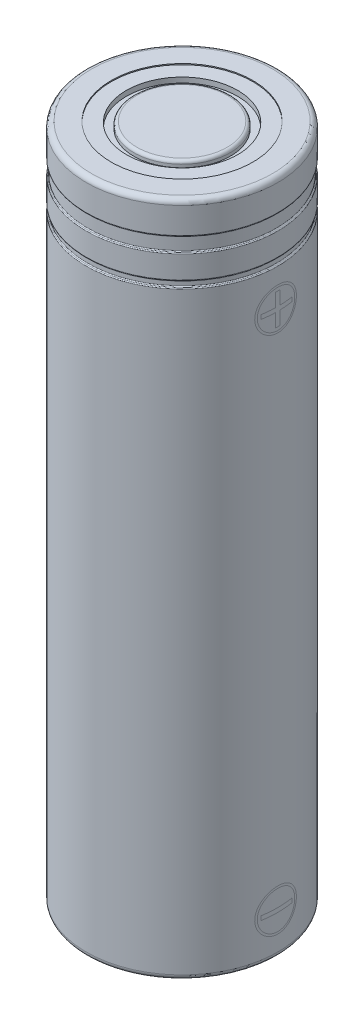
SolidWorks part; units mm, degrees
ref_plane "Front Plane" through (0, 0, 0) normal (0, 0, 1) x (1, 0, 0)
ref_plane "Top Plane" through (0, 0, 0) normal (0, 1, 0) x (1, 0, 0)
ref_plane "Right Plane" through (0, 0, 0) normal (1, 0, 0) x (0, 0, -1)
sketch "Sketch1" plane through (0, 0, 0) normal (0, 0, 1) x (1, 0, 0)
  line L0 (0, 0) -> (0, -7.4) construction
  line L1 (9.2, 57.54) -> (9.2, 0.5)
  line L4 (9.06, 58.1092) -> (9.06, 57.7308)
  line L6 (9.2, 60.46) -> (9.2, 58.3)
  line L8 (9.06, 61.8092) -> (9.06, 60.6508)
  line L9 (9.2, 64.5) -> (9.2, 62)
  line L12 (8.7, 65) -> (6.8, 65)
  line L14 (6.8, 64.9) -> (6.8, 65)
  line L16 (6.8, 64.9) -> (5.35, 64.9)
  line L18 (5.35, 64.4) -> (5.35, 64.9)
  line L20 (5.35, 64.4) -> (4.63, 64.4)
  line L22 (4.63, 64.4) -> (4.63, 64.7)
  line L23 (4.33, 65) -> (0, 65)
  line L25 (8.7, 0) -> (7.9, 0)
  line L27 (7.4, 0) -> (7.4, 0.1)
  line L29 (7.9, 0.1) -> (7.4, 0.1)
  line L32 (0, 0) -> (7.4, 0)
  line L33 (7.9, 0.1) -> (7.9, 0)
  line L34 (0, 65) -> (0, 0)
  line L35 (9.06, 61.8092) -> (9.2, 62) construction
  line L36 (8.7, 64.9) -> (6.8, 64.9)
  line L37 (9.1, 64.5) -> (9.1, 62)
  line L38 (8.96, 61.8092) -> (8.96, 60.6508)
  line L39 (9.1, 60.46) -> (9.1, 58.3)
  line L40 (8.96, 58.1092) -> (8.96, 57.7308)
  line L41 (9.1, 57.54) -> (9.1, 0.5)
  line L42 (8.7, 0.1) -> (7.9, 0.1)
  arc A1 (9.2, 57.54) -> (9.13, 57.6354) centre (9.1, 57.54) ccw
  arc A2 (9.06, 57.7308) -> (9.13, 57.6354) centre (9.16, 57.7308) ccw
  arc A4 (9.13, 58.2046) -> (9.06, 58.1092) centre (9.16, 58.1092) ccw
  arc A6 (9.13, 58.2046) -> (9.2, 58.3) centre (9.1, 58.3) ccw
  arc A9 (9.2, 60.46) -> (9.13, 60.5554) centre (9.1, 60.46) ccw
  arc A10 (9.06, 60.6508) -> (9.13, 60.5554) centre (9.16, 60.6508) ccw
  arc A13 (9.13, 61.9046) -> (9.06, 61.8092) centre (9.16, 61.8092) ccw
  arc A15 (9.13, 61.9046) -> (9.2, 62) centre (9.1, 62) ccw
  arc A17 (9.2, 64.5) -> (8.7, 65) centre (8.7, 64.5) ccw
  arc A19 (4.63, 64.7) -> (4.33, 65) centre (4.33, 64.7) ccw
  arc A21 (8.7, 0) -> (9.2, 0.5) centre (8.7, 0.5) ccw
  arc A22 (9.1, 64.5) -> (8.7, 64.9) centre (8.7, 64.5) ccw
  arc A23 (9.1, 62) -> (8.96, 61.8092) centre (9.16, 61.8092) ccw
  arc A24 (8.96, 60.6508) -> (9.1, 60.46) centre (9.16, 60.6508) ccw
  arc A25 (9.1, 58.3) -> (8.96, 58.1092) centre (9.16, 58.1092) ccw
  arc A26 (8.96, 57.7308) -> (9.1, 57.54) centre (9.16, 57.7308) ccw
  arc A27 (8.7, 0.1) -> (9.1, 0.5) centre (8.7, 0.5) ccw
  point P0 (7.9, 0.05)
  point P3 (3.7, 0)
  dimension "D1" = 0.5
  dimension "D3" = 0.5
  dimension "D4" = 0.3
  dimension "D5" = 0.1
  dimension "D2" = 65
  dimension "D6" = 18.4
  dimension "D7" = 0.5
  dimension "D8" = 0.1
  dimension "D9" = 14.8
  dimension "D10" = 9.26
  dimension "D11" = 10.7
  dimension "D12" = 0.1
  dimension "D13" = 0.6
  dimension "D14" = 13.6
  dimension "D15" = 0.14
  dimension "D16" = 1.54
  dimension "D17" = 0.76
  dimension "D18" = 6.7
  dimension "D19" = 3
  dimension "D20" = 0.1
  dimension "D21" = 0.1
revolve "Revolve1" add sketch "Sketch1" angle 360 about L0 region at (4.5442, 32.4503, 0)
revolve "Revolve2" add sketch "Sketch1<3>" angle 360 about L0 region at (9.135, 29.02, 0)
sketch "Sketch1<3>" plane through (0, 0, 0) normal (0, 0, 1) x (1, 0, 0) same geometry as "Sketch1"
sketch "Sketch2" plane through (0, 0, 0) normal (1, 0, 0) x (0, 0, -1)
  line B0 (-0.2, 54.2) -> (-0.2, 55.4866)
  line B1 (-0.2, 54.2) -> (0.2, 54.2) construction
  line B2 (-0.2, 54.2) -> (-0.2, 53.8) construction
  line B3 (-0.2, 53.8) -> (0.2, 53.8) construction
  line B4 (0.2, 54.2) -> (0.2, 53.8) construction
  line B5 (-0.2, 54.2) -> (0.2, 53.8) construction
  line B6 (-0.2, 53.8) -> (0.2, 54.2) construction
  line B7 (-0.2, 55.4866) -> (0.2, 55.4866)
  line B8 (0.2, 55.4866) -> (0.2, 54.2)
  line B9 (0.2, 53.8) -> (1.4866, 53.8)
  line B10 (1.4866, 53.8) -> (1.4866, 54.2)
  line B11 (1.4866, 54.2) -> (0.2, 54.2)
  line B12 (-0.2, 54.2) -> (-1.4866, 54.2)
  line B13 (-1.4866, 54.2) -> (-1.4866, 53.8)
  line B14 (-1.4866, 53.8) -> (-0.2, 53.8)
  line B15 (-0.2, 52.5134) -> (0.2, 52.5134)
  line B16 (0.2, 52.5134) -> (0.2, 53.8)
  line B17 (-0.2, 53.8) -> (-0.2, 52.5134)
  circle B18 centre (0, 54) radius 2
  circle B19 centre (0, 54) radius 1.8
  circle B20 centre (0, 54) radius 1.5 construction
  line B21 (-0.2, 4.2) -> (-0.2, 5.4866) construction
  line B22 (-0.2, 4.2) -> (0.2, 4.2)
  line B23 (-0.2, 4.2) -> (-0.2, 3.8) construction
  line B24 (-0.2, 3.8) -> (0.2, 3.8)
  line B25 (0.2, 4.2) -> (0.2, 3.8) construction
  line B26 (-0.2, 4.2) -> (0.2, 3.8) construction
  line B27 (-0.2, 3.8) -> (0.2, 4.2) construction
  line B28 (-0.2, 5.4866) -> (0.2, 5.4866) construction
  line B29 (0.2, 5.4866) -> (0.2, 4.2) construction
  line B30 (0.2, 3.8) -> (1.4866, 3.8)
  line B31 (1.4866, 3.8) -> (1.4866, 4.2)
  line B32 (1.4866, 4.2) -> (0.2, 4.2)
  line B33 (-0.2, 4.2) -> (-1.4866, 4.2)
  line B34 (-1.4866, 4.2) -> (-1.4866, 3.8)
  line B35 (-1.4866, 3.8) -> (-0.2, 3.8)
  line B36 (-0.2, 2.5134) -> (0.2, 2.5134) construction
  line B37 (0.2, 2.5134) -> (0.2, 3.8) construction
  line B38 (-0.2, 3.8) -> (-0.2, 2.5134) construction
  circle B39 centre (0, 4) radius 2
  circle B40 centre (0, 4) radius 1.8
  circle B41 centre (0, 4) radius 1.5 construction
  dimension "D1" = 4
  dimension "D2" = 54
sketch_block_instance "Plus_Sign-1"
sketch_block "Plus_Sign" parameters "D2"=2, "D1"=1.8, "D3"=1.65, "D4"=0.2
sketch_block_instance "Minus_Sign-1"
sketch_block "Minus_Sign" parameters "D1"=2, "D2"=1.65, "D3"=0.2, "D4"=0.1
split line "Split Line1"
